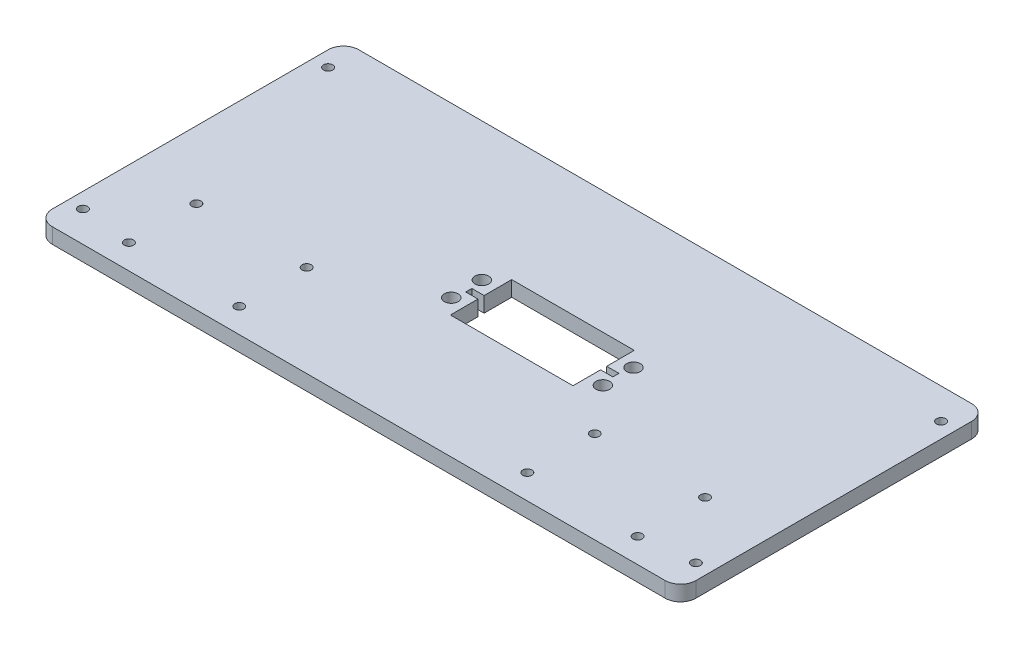
SolidWorks part; units mm, degrees
ref_plane "前视基准面" through (0, 0, 0) normal (0, 0, 1) x (1, 0, 0)
ref_plane "上视基准面" through (0, 0, 0) normal (0, 1, 0) x (1, 0, 0)
ref_plane "右视基准面" through (0, 0, 0) normal (1, 0, 0) x (0, 0, -1)
other "Configuration Table"
sketch "草图1" plane through (0, 0, 0) normal (0, 1, 0) x (1, 0, 0)
  line L1 (-210, 100) -> (0, 100)
  line L2 (-210, 100) -> (-210, 0)
  line L3 (-210, 0) -> (0, 0)
  line L4 (0, 100) -> (0, 0)
  dimension "D1" = 210
  dimension "D2" = 100
extrude "凸台-拉伸1" add sketch "草图1" along normal blind 5
fillet "圆角1" radius 5 4 edges at (0, 2.5, -100) (-210, 2.5, -100) (-210, 2.5, 0) (0, 2.5, 0)
sketch "草图2" plane through (0, 5, 0) normal (0, 1, 0) x (1, 0, 0)
  line L0 (-5, 100) -> (-205, 100) construction
  line L1 (-210, 95) -> (-210, 5) construction
  line L2 (-105, 100) -> (-105, 0) construction
  line L3 (-205, 0) -> (-5, 0) construction
  line L4 (-210, 50) -> (0, 50) construction
  line L5 (0, 5) -> (0, 95) construction
  circle A0 centre (-205, 90) radius 1.5
  circle A1 centre (-205, 10) radius 1.5
  circle A2 centre (-5, 10) radius 1.5
  circle A3 centre (-5, 90) radius 1.5
  dimension "D1" = 3
  dimension "D2" = 10
  dimension "D3" = 5
extrude "切除-拉伸1" cut sketch "草图2" against normal up to surface (5 mm away) up to face at (-105, 0, -50)
sketch "草图4" plane through (0, 0, 0) normal (0, -1, 0) x (1, 0, 0)
  line L0 (-5, -100) -> (-205, -100) construction
  line L1 (-115.1, -60) -> (-75.1, -60)
  line L2 (-115.1, -60) -> (-115.1, -51)
  line L3 (-115.1, -40) -> (-75.1, -40)
  line L4 (-75.1, -60) -> (-75.1, -51)
  line L5 (-210, -95) -> (-210, -5) construction
  line L6 (-205, 0) -> (-5, 0) construction
  line L7 (0, -5) -> (0, -95) construction
  line L8 (-119.1, -50) -> (-71.1, -50) construction
  line L9 (-95.1, -40) -> (-95.1, -60) construction
  line L10 (-115.1, -49) -> (-119.1, -49)
  line L11 (-115.1, -51) -> (-119.1, -51)
  line L12 (-119.1, -49) -> (-119.1, -51)
  line L13 (-75.1, -51) -> (-71.1, -51)
  line L14 (-71.1, -49) -> (-71.1, -51)
  line L15 (-75.1, -49) -> (-71.1, -49)
  line L16 (-115.1, -49) -> (-115.1, -40)
  line L17 (-75.1, -49) -> (-75.1, -40)
  circle A0 centre (-119.85, -45) radius 2.25
  circle A1 centre (-119.85, -55) radius 2.25
  circle A2 centre (-70.35, -55) radius 2.25
  circle A3 centre (-70.35, -45) radius 2.25
  dimension "D6" = 4.5
  dimension "D1" = 40
  dimension "D2" = 94.9
  dimension "D3" = 40
  dimension "D4" = 75.1
  dimension "D5" = 49.5
  dimension "D7" = 10
  dimension "D8" = 2
  dimension "D9" = 4
  dimension "D10" = 10
extrude "切除-拉伸2" cut sketch "草图4" against normal up to surface (5 mm away) up to face at (-5, 5, -91.5)
sketch "草图6" plane through (0, 0, 0) normal (0, -1, 0) x (1, 0, 0)
  line L0 (-210, -95) -> (-210, -5) construction
  line L1 (-5, -100) -> (-205, -100) construction
  line L3 (-105, 0) -> (-105, -100) construction
  line L4 (-205, 0) -> (-5, 0) construction
  circle A4 centre (-188, -30) radius 1.5
  circle A5 centre (-188, -8) radius 1.5
  circle A6 centre (-152, -30) radius 1.5
  circle A7 centre (-152, -8) radius 1.5
  circle A8 centre (-58, -30) radius 1.5
  circle A9 centre (-22, -30) radius 1.5
  circle A10 centre (-58, -8) radius 1.5
  circle A11 centre (-22, -8) radius 1.5
  point P2 (-152, -50)
  point P3 (0, 0)
  point P4 (-152.028, -29.4208)
  point P7 (0, 0)
  point P8 (-152, -28)
  point P13 (0, 0)
  dimension "D2" = 70
  dimension "D3" = 22
  dimension "D6" = 3
  dimension "D7" = 3
  dimension "D8" = 22
  dimension "D10" = 36
extrude "切除-拉伸3" cut sketch "草图6" against normal up to surface (5 mm away) up to face at (-70.35, 5, -42.75)
